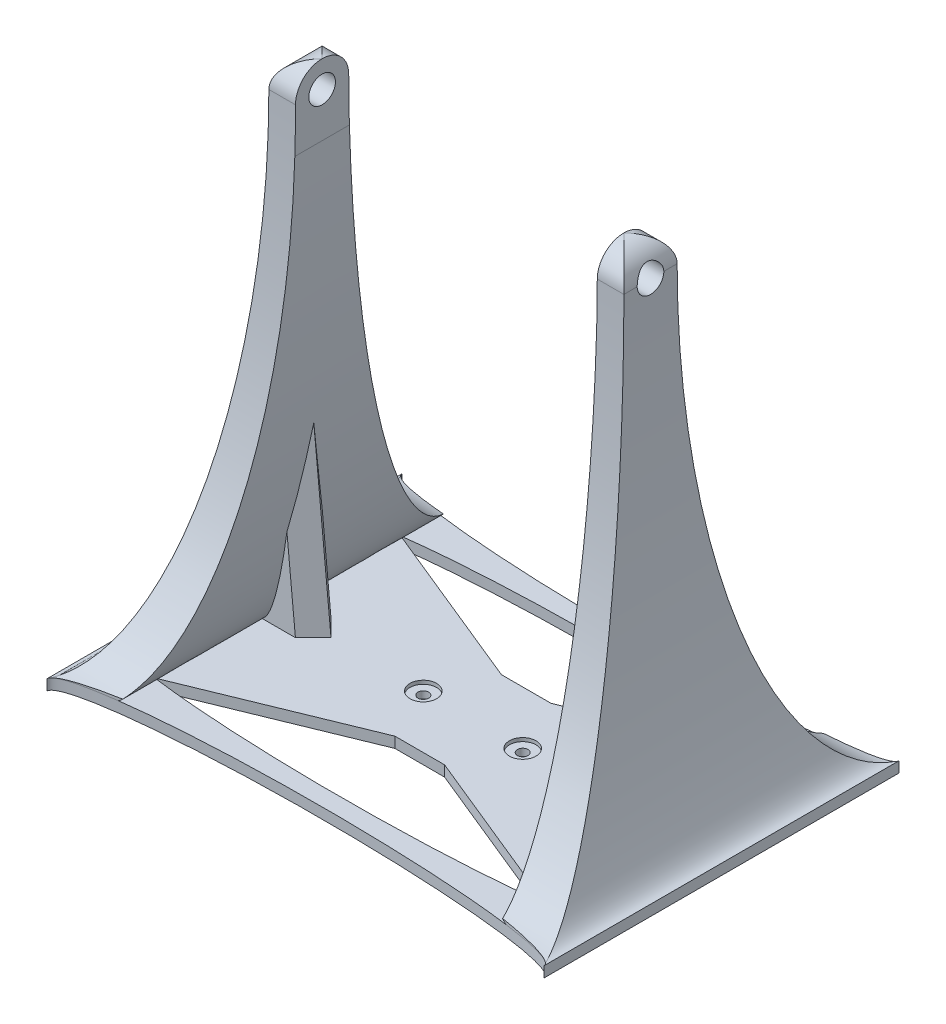
SolidWorks part; units mm, degrees
ref_plane "Front Plane" through (0, 0, 0) normal (0, 0, 1) x (1, 0, 0)
ref_plane "Top Plane" through (0, 0, 0) normal (0, 1, 0) x (1, 0, 0)
ref_plane "Right Plane" through (0, 0, 0) normal (1, 0, 0) x (0, 0, -1)
sketch "Sketch1" plane through (0, 0, 0) normal (0, 1, 0) x (1, 0, 0)
  line L0 (0, 57.5) -> (0, 42.5) construction
  line L1 (-14, 0) -> (-7, 15) construction
  line L2 (-7, 15) -> (-55, 34.6394)
  line L3 (-70, 30) -> (-70, 50) construction
  line L4 (-70, 50) -> (0, 50) construction
  line L5 (0, 0) -> (-47.9407, 0) construction
  line L6 (-70, 50) -> (-70, -50)
  line L7 (0, 42.5) -> (0, 37.5) construction
  line L8 (-7, 15) -> (0, 0) construction
  line L9 (-7, 15) -> (7, 15)
  line L10 (70, 30) -> (70, 50) construction
  line L11 (0, 22.5) -> (0, 37.5) construction
  line L12 (-70, 30) -> (0, 30) construction
  line L13 (14, 0) -> (7, 15) construction
  line L14 (70, 50) -> (70, -50)
  line L15 (7, 15) -> (55, 34.6394)
  line L16 (14, 0) -> (7, -15) construction
  line L17 (-70, -30) -> (0, -30) construction
  line L18 (0, -22.5) -> (0, -37.5) construction
  line L19 (70, -30) -> (70, -50) construction
  line L20 (-7, -15) -> (0, 0) construction
  line L21 (0, -42.5) -> (0, -37.5) construction
  line L22 (-70, -50) -> (0, -50) construction
  line L23 (-70, -30) -> (-70, -50) construction
  line L24 (-14, 0) -> (-7, -15) construction
  line L25 (0, -57.5) -> (0, -42.5) construction
  line L26 (7, -15) -> (55, -34.6394)
  line L27 (-7, -15) -> (7, -15)
  line L28 (-7, -15) -> (-55, -34.6394)
  ellipse E0 centre (0, 50) end of major axis (70, 50) minor radius 7.5 (-70, 50) -> (70, 50) ccw
  ellipse E1 centre (0, 30) end of major axis (-70, 30) minor radius 7.5 (55, 34.6394) -> (-55, 34.6394) ccw
  ellipse E2 centre (0, -30) end of major axis (-70, -30) minor radius 7.5 (55, -34.6394) -> (-55, -34.6394) cw
  ellipse E3 centre (0, -50) end of major axis (70, -50) minor radius 7.5 (-70, -50) -> (70, -50) cw
  point P0 (0, 40)
  point P12 (97.9451, 0)
  point P29 (0, 15)
  point P32 (-70, 0)
  point P57 (70, 0)
  line B0 (-14, 0) -> (0, 0) construction
  line B1 (0, 0) -> (14, 0) construction
  circle B2 centre (14, 0) radius 1.5
  circle B3 centre (-14, 0) radius 1.5
  line B4 (14, 0) -> (0, 0) construction
  line B5 (0, 0) -> (-14, 0) construction
  circle B6 centre (-14, 0) radius 1.5
  circle B7 centre (14, 0) radius 1.5
  dimension "D3" = 25
  dimension "D1" = 5
  dimension "D2" = 20
  dimension "D4" = 50
  dimension "D5" = 15
  dimension "D6" = 15
  dimension "D7" = 70
sketch_block_instance "Block1-1"
sketch_block "Block1"
sketch_block_instance "Block1-5"
extrude "Boss-Extrude1" add sketch "Sketch1" along normal blind 3 contours E0 E1 L9 L2 region at (0, 0, 0)
sketch "Sketch2" plane through (0, 3, 0) normal (0, 1, 0) x (1, 0, 0)
  circle A0 centre (-14, 0) radius 3.75
  circle A1 centre (14, 0) radius 3.75
  dimension "D1" = 7.5
extrude "Cut-Extrude1" cut sketch "Sketch2" against normal blind 1
sketch "Sketch3" plane through (0, 0, 0) normal (0, 0, 1) x (1, 0, 0)
  line L0 (-50, 135.5) -> (-90, 135.5) construction
  line L1 (-42.5, 143) -> (-42.5, 123)
  line L2 (-67.5, 123) -> (-42.5, 123) construction
  line L3 (70, 3) -> (-70, 3) construction
  line L4 (0, 0) -> (0, 59.5964) construction
  line L5 (-70, 3) -> (-55, 3)
  line L6 (-55, 123) -> (-55, 3) construction
  line L7 (55, 123) -> (55, 3) construction
  line L8 (67.5, 123) -> (42.5, 123) construction
  line L9 (70, 3) -> (55, 3)
  line L10 (42.5, 143) -> (42.5, 123)
  arc A0 (-42.5244, 128) -> (-42.5, 128) centre (-42.5, 135.5) ccw
  arc A1 (-42.5, 143) -> (-50, 135.5) centre (-42.5, 135.5) ccw
  arc A2 (42.5, 143) -> (50, 135.5) centre (42.5, 135.5) cw
  arc A3 (42.5244, 128) -> (42.5, 128) centre (42.5, 135.5) cw
  ellipse E0 centre (55, 123) end of major axis (55, 243) minor radius 12.5 (55, 3) -> (42.5, 123) cw
  ellipse E1 centre (-70, 135.5) end of major axis (-70, 268) minor radius 20 (-70, 3) -> (-50, 135.5) ccw
  ellipse E2 centre (-55, 123) end of major axis (-55, 243) minor radius 12.5 (-55, 3) -> (-42.5, 123) ccw
  ellipse E3 centre (70, 135.5) end of major axis (70, 268) minor radius 20 (70, 3) -> (50, 135.5) cw
  dimension "D5" = 15
  dimension "D1" = 42.5
  dimension "D2" = 20
  dimension "D3" = 140
  dimension "D4" = 15
  dimension "D6" = 85
  dimension "D7" = 7.5
extrude "Boss-Extrude2" add sketch "Sketch3" along normal blind 50 and the other way blind 50 contours L5 E2 L1 A1 E1 | L9 E3 A2 L10 E0 region at (-50.108, 65.2961, 0) region at (50.108, 65.2961, 0)
sketch "Sketch4" plane through (0, 0, 0) normal (1, 0, 0) x (0, 0, -1)
  line L0 (0, 0) -> (0, -6.4833) construction
  line L1 (-50, 3) -> (-50, 143)
  line L2 (-50, 143) -> (50, 143)
  line L3 (50, 3) -> (50, 143)
  line L5 (50, 135.5) -> (-50, 135.5) construction
  arc A0 (7.5, 135.5) -> (-7.5, 135.5) centre (0, 135.5) ccw
  circle A1 centre (0, 135.5) radius 3.75
  ellipse E0 centre (-50, 135.5) end of major axis (-50, 268) minor radius 42.5 (-50, 3) -> (-7.5, 135.5) ccw
  ellipse E1 centre (50, 135.5) end of major axis (50, 268) minor radius 42.5 (50, 3) -> (7.5, 135.5) cw
  point P25 (0, 143)
  dimension "D1" = 15
  dimension "D2" = 7.5
extrude "Cut-Extrude2" cut sketch "Sketch4" against normal blind 100 and the other way blind 100 contours L1 E0 A0 L2 | E1 L3 L2 A0 | A1 region at (0, 83.4451, -31.6807) region at (0, 83.4451, 31.6807)
sketch "Sketch5" plane through (0, 0, 0) normal (0, -1, 0) x (1, 0, 0)
  line L0 (-70, 50) -> (-55, 50) construction
  ellipse E0 centre (0, 50) end of major axis (-70, 50) minor radius 7.5
  ellipse E1 centre (0, 50) end of major axis (70, 50) minor radius 7.5 (-70, 50) -> (70, 50) ccw construction
  ellipse E2 centre (0, -50) end of major axis (-70, -50) minor radius 7.5
extrude "Cut-Extrude3" cut sketch "Sketch5" against normal blind 50
sketch "Sketch7" plane through (0, 0, 0) normal (0, 0, 1) x (1, 0, 0)
  line L0 (-62.5, 3) -> (-44.8471, 53)
  line L1 (-70, 3) -> (-55, 3) construction
  line L2 (-44.8471, 53) -> (-40, 3)
  line L3 (55, 3) -> (-55, 3) construction
  line L4 (-40, 3) -> (-62.5, 3)
  line L5 (-40, 148) -> (40, 148) construction
  line L6 (-40, 227.6) -> (40, 227.6) construction
  line L7 (-40, 227.6) -> (-40, 17.6) construction
  line L8 (-40, 17.6) -> (40, 17.6) construction
  line L9 (40, 227.6) -> (40, 17.6) construction
  line L10 (-40, 97.2) -> (40, 122.6) construction
  line L11 (-40, 97.2) -> (40, 97.2) construction
  line L12 (40, 122.6) -> (-40, 148) construction
  line L13 (-42.5, 135.5) -> (-40, 135.5) construction
  line L14 (0, 0) -> (0, -33.258) construction
  line L15 (40, 3) -> (62.5, 3)
  line L16 (42.5, 135.5) -> (40, 135.5) construction
  line L17 (44.8471, 53) -> (40, 3)
  line L18 (62.5, 3) -> (44.8471, 53)
  ellipse E0 centre (-55, 123) end of major axis (-55, 243) minor radius 12.5 (-53.5057, 3.8605) -> (-42.5, 123) ccw construction
  point P29 (-51.25, 3)
  dimension "D1" = 210
  dimension "D2" = 80
  dimension "D3" = 50.8
  dimension "D4" = 50
  dimension "D5" = 5
  dimension "D6" = 22.5
extrude "Boss-Extrude3" add sketch "Sketch7" along normal blind 5 and the other way blind 5
chamfer "Chamfer1" distance 5 angle 45 4 edges at (42.4235, 28, -5) (42.4235, 28, 5) (-42.4235, 28, -5) (-42.4235, 28, 5)
